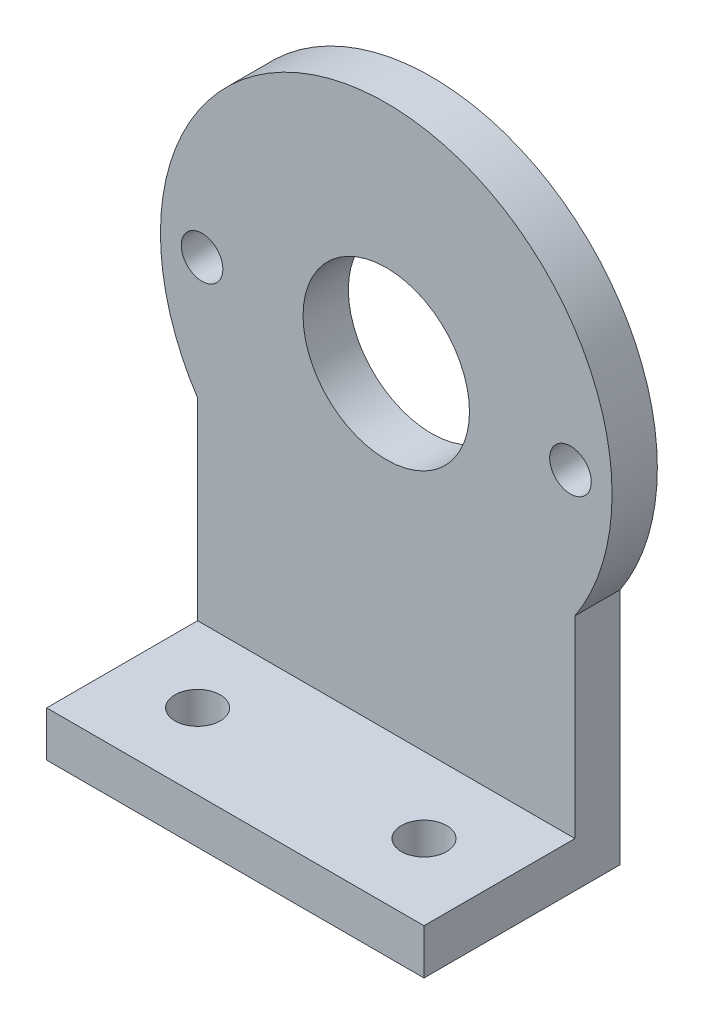
SolidWorks part; units mm, degrees
ref_plane "Front Plane" through (0, 0, 0) normal (0, 0, 1) x (1, 0, 0)
ref_plane "Top Plane" through (0, 0, 0) normal (0, 1, 0) x (1, 0, 0)
ref_plane "Right Plane" through (0, 0, 0) normal (1, 0, 0) x (0, 0, -1)
sketch "Sketch1" plane through (0, 0, 0) normal (0, 0, 1) x (1, 0, 0)
  line L1 (-15.875, -10.4396) -> (15.875, -10.4396)
  line L2 (-15.875, -10.4396) -> (-15.875, -30.48)
  line L3 (-15.875, -30.48) -> (15.875, -30.48)
  line L4 (15.875, -10.4396) -> (15.875, -30.48)
  circle A0 centre (0, 0) radius 19
  arc A2 (-15.875, -10.4396) -> (15.875, -10.4396) centre (0, 0) ccw
  dimension "D1" = 38
  dimension "D2" = 30.48
  dimension "D3" = 31.75
extrude "Boss-Extrude1" add sketch "Sketch1" along normal blind 3.81 contours A0 | L2 L1 L4 L3
sketch "Sketch3" plane through (0, 0, 3.81) normal (0, 0, 1) x (1, 0, 0)
  circle A0 centre (0, 0) radius 7
  dimension "D1" = 14
extrude "Cut-Extrude1" cut sketch "Sketch3" against normal through all
sketch "Sketch4" plane through (0, 0, 3.81) normal (0, 0, 1) x (1, 0, 0)
  line L0 (15.875, -10.4396) -> (15.875, -30.48) construction
  line L1 (-15.875, -30.48) -> (15.875, -30.48)
  line L2 (-15.875, -30.48) -> (-15.875, -26.67)
  line L3 (-15.875, -26.67) -> (15.875, -26.67)
  line L4 (15.875, -30.48) -> (15.875, -26.67)
  dimension "D1" = 3.81
extrude "Boss-Extrude2" add sketch "Sketch4" along normal blind 12.7
sketch "Sketch5" plane through (0, -26.67, 0) normal (0, 1, 0) x (1, 0, 0)
  line L0 (-15.875, -10.16) -> (15.875, -10.16) construction
  line L1 (-15.875, -16.51) -> (-15.875, -3.81) construction
  line L2 (15.875, -16.51) -> (15.875, -3.81) construction
  line L3 (0, -3.81) -> (0, -16.51) construction
  line L4 (15.875, -3.81) -> (-15.875, -3.81) construction
  line L5 (15.875, -16.51) -> (-15.875, -16.51) construction
  circle A0 centre (-9.525, -10.16) radius 1.905
  circle A1 centre (9.525, -10.16) radius 1.905
  dimension "D1" = 3.81
  dimension "D2" = 9.525
extrude "Cut-Extrude2" cut sketch "Sketch5" against normal through all
sketch "Sketch6" plane through (0, 0, 3.81) normal (0, 0, 1) x (1, 0, 0)
  line L0 (0, 19) -> (0, -26.67) construction
  line L1 (15.875, -26.67) -> (-15.875, -26.67) construction
  circle A0 centre (0, 0) radius 15.5 construction
  circle A1 centre (15.5, 0) radius 1.75
  arc A2 (15.875, -10.4396) -> (-15.875, -10.4396) centre (0, 0) ccw construction
  circle A3 centre (-15.5, 0) radius 1.75
  dimension "D1" = 31
  dimension "D2" = 3.5
extrude "Cut-Extrude3" cut sketch "Sketch6" against normal through all
